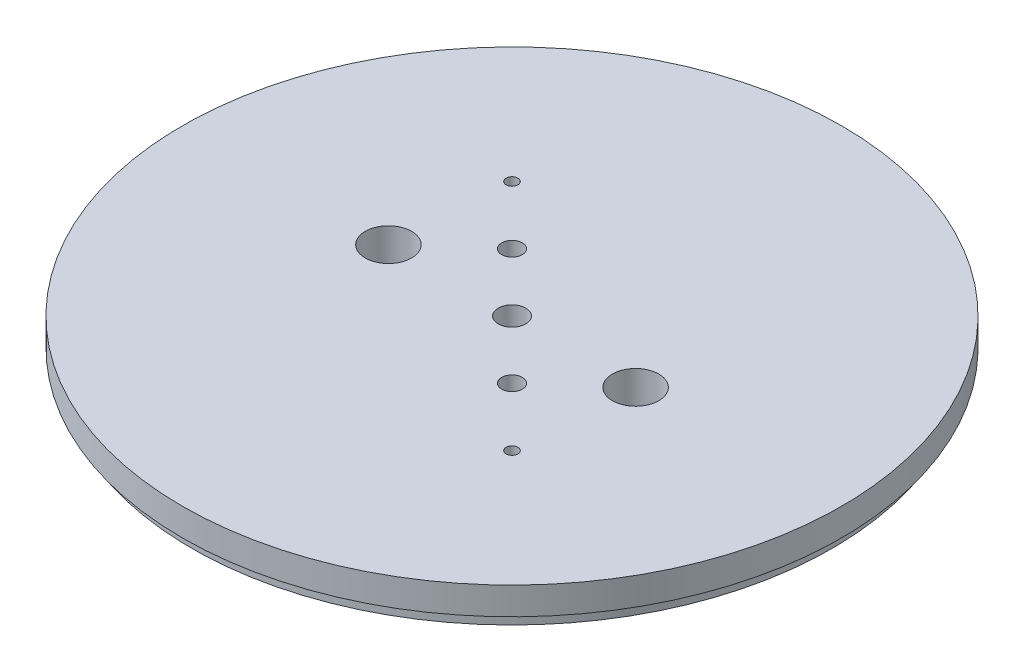
SolidWorks part; units mm, degrees
ref_plane "Front Plane" through (0, 0, 0) normal (0, 0, 1) x (1, 0, 0)
ref_plane "Top Plane" through (0, 0, 0) normal (0, 1, 0) x (1, 0, 0)
ref_plane "Right Plane" through (0, 0, 0) normal (1, 0, 0) x (0, 0, -1)
sketch "Sketch1" plane through (0, 0, 0) normal (0, 1, 0) x (1, 0, 0)
  line L0 (0, -76.2) -> (0, 76.2) construction
  line L1 (-76.2, 0) -> (76.2, 0) construction
  line L2 (-26.9408, 26.9408) -> (0, 0) construction
  line L3 (0, 56.7387) -> (0, 29.6936) construction
  line L4 (3.6407, 56.7387) -> (3.6407, 29.6936) construction
  line L5 (-3.6407, 56.7387) -> (-3.6407, 29.6936) construction
  line L6 (0, -56.7387) -> (0, -29.6936) construction
  line L7 (3.6407, -56.7387) -> (3.6407, -29.6936) construction
  line L8 (-3.6407, -56.7387) -> (-3.6407, -29.6936) construction
  line L9 (-53.8815, -53.8815) -> (54.3236, 54.3236) construction
  circle A0 centre (0, 0) radius 76.2
  circle A1 centre (0, 0) radius 3.175
  circle A2 centre (28.575, 0) radius 5.3578
  circle A3 centre (-28.575, 0) radius 5.3578
  circle A4 centre (-26.9408, 26.9408) radius 1.3589
  arc A6 (3.6407, 56.7387) -> (-3.6407, 56.7387) centre (0, 56.7387) ccw construction
  arc A7 (-3.6407, 29.6936) -> (3.6407, 29.6936) centre (0, 29.6936) ccw construction
  arc A8 (3.6407, -56.7387) -> (-3.6407, -56.7387) centre (0, -56.7387) cw construction
  arc A9 (-3.6407, -29.6936) -> (3.6407, -29.6936) centre (0, -29.6936) cw construction
  circle A10 centre (26.9408, -26.9408) radius 1.3589
  circle A11 centre (-13.4704, 13.4704) radius 2.3813
  circle A12 centre (13.4704, -13.4704) radius 2.3813
  point P16 (0, 43.2162)
  point P19 (0, 0)
  point P26 (0, -43.2162)
  dimension "D1" = 152.4
  dimension "D2" = 6.35
  dimension "D3" = 10.7156
  dimension "D5" = 2.7178
  dimension "D8" = 4.7625
  dimension "D6" = 38.1
  dimension "D7" = 45
  dimension "D4" = 45
  dimension "D9" = 28.575
extrude "Boss-Extrude1" add sketch "Sketch1" along normal blind 9.525
sketch "Sketch2" plane through (0, 0, 0) normal (0, -1, 0) x (1, 0, 0)
  circle A0 centre (0, 0) radius 76.2
  circle A1 centre (0, 0) radius 74.041
  dimension "D1" = 152.4
  dimension "D2" = 148.082
extrude "Cut-Extrude1" cut sketch "Sketch2" against normal blind 3.175
sketch "Sketch3" plane through (0, 9.525, 0) normal (0, 1, 0) x (1, 0, 0)
  line L0 (0, 76.2) -> (0, -76.2) construction
  line L1 (-76.2, 0) -> (76.2, 0) construction
  line L2 (0, 34.798) -> (0, 13.97) construction
  line L3 (3.2385, 34.798) -> (3.2385, 13.97)
  line L4 (-3.2385, 34.798) -> (-3.2385, 13.97)
  line L5 (0, -34.798) -> (0, -13.97) construction
  line L6 (3.2385, -34.798) -> (3.2385, -13.97)
  line L7 (-3.2385, -34.798) -> (-3.2385, -13.97)
  circle A0 centre (0, 0) radius 76.2 construction
  arc A1 (3.2385, 34.798) -> (-3.2385, 34.798) centre (0, 34.798) ccw
  arc A2 (-3.2385, 13.97) -> (3.2385, 13.97) centre (0, 13.97) ccw
  arc A3 (3.2385, -34.798) -> (-3.2385, -34.798) centre (0, -34.798) cw
  arc A4 (-3.2385, -13.97) -> (3.2385, -13.97) centre (0, -13.97) cw
  point P7 (0, 13.97)
  point P8 (0, 34.798)
  point P12 (0, 24.384)
  point P20 (0, -24.384)
  point P25 (0, -34.798)
  point P26 (0, -13.97)
  dimension "D1" = 13.97
  dimension "D2" = 20.828
  dimension "D3" = 6.477
extrude "Cut-Extrude2" cut sketch "Sketch3" against normal blind 3.556 from offset 5.969 offset against normal yes
equation "\"leadDist\"=1.5"
equation "\"Lead_Screw_Dist\" = 2.25in"
equation "\"D9@Sketch1\"=\"Lead_Screw_Dist\"/2"
equation "\"Lead_Screw_Diam\" = (27/64)*1in"
equation "\"D3@Sketch1\"=\"Lead_Screw_Diam\""
